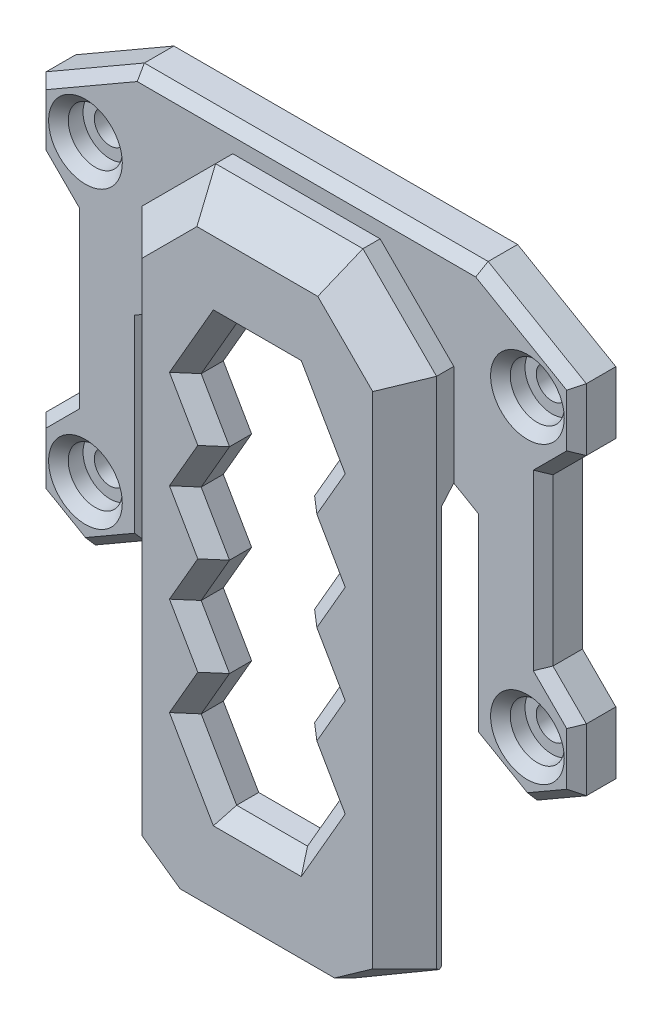
SolidWorks part; units mm, degrees
ref_plane "Front Plane" through (0, 0, 0) normal (0, 0, 1) x (1, 0, 0)
ref_plane "Top Plane" through (0, 0, 0) normal (0, 1, 0) x (1, 0, 0)
ref_plane "Right Plane" through (0, 0, 0) normal (1, 0, 0) x (0, 0, -1)
sketch "Sketch1" plane through (0, 0, 0) normal (0, 0, 1) x (1, 0, 0)
  line L0 (17.5, 0) -> (-17.5, 0)
  line L1 (-17.5, 0) -> (-27.5, -5.7735)
  line L2 (-27.5, -5.7735) -> (-27.5, -12.1132)
  line L3 (-27.5, -12.1132) -> (-24.1, -15.5132)
  line L4 (-24.1, -15.5132) -> (-24.1, -32.3735)
  line L5 (-24.1, -32.3735) -> (-27.5, -35.7735)
  line L6 (-27.5, -35.7735) -> (-27.5, -42.1132)
  line L7 (-27.5, -42.1132) -> (-22.5, -45)
  line L9 (-17.5, -42.1132) -> (-17.5, -20)
  line L10 (-4.5096, -12.5) -> (4.5096, -12.5)
  line L11 (0, -12.5) -> (0, 0) construction
  line L12 (-22.5, -45) -> (-17.5, -42.1132)
  line L13 (22.5, -45) -> (17.5, -42.1132)
  line L14 (17.5, -42.1132) -> (17.5, -20)
  line L15 (27.5, -42.1132) -> (22.5, -45)
  line L16 (27.5, -35.7735) -> (27.5, -42.1132)
  line L17 (24.1, -32.3735) -> (27.5, -35.7735)
  line L18 (24.1, -15.5132) -> (24.1, -32.3735)
  line L19 (27.5, -12.1132) -> (24.1, -15.5132)
  line L20 (27.5, -5.7735) -> (27.5, -12.1132)
  line L21 (17.5, 0) -> (27.5, -5.7735)
  line L22 (-17.5, -20) -> (-4.5096, -12.5)
  line L23 (4.5096, -12.5) -> (17.5, -20)
  circle A0 centre (-22.5, -8.9434) radius 1.6
  circle A1 centre (-22.5, -38.9434) radius 1.6
  circle A4 centre (22.5, -38.9434) radius 1.6
  circle A5 centre (22.5, -8.9434) radius 1.6
  point P18 (-27.5, -38.9434)
  point P35 (-27.5, -8.9434)
  dimension "D5" = 3.2
  dimension "D11" = 7.5
  dimension "D1" = 17.5
  dimension "D2" = 150
  dimension "D3" = 135
  dimension "D4" = 22.5
  dimension "D6" = 30
  dimension "D7" = 60
  dimension "D8" = 10
  dimension "D9" = 120
  dimension "D10" = 45
  dimension "D12" = 12.5
  dimension "D13" = 150
extrude "Boss-Extrude1" add sketch "Sketch1" along normal blind 4
sketch "Sketch2" plane through (0, 0, 4) normal (0, 0, 1) x (1, 0, 0)
  circle A0 centre (-22.5, -8.9434) radius 2.75
  circle A1 centre (22.5, -8.9434) radius 2.75
  circle A2 centre (22.5, -38.9434) radius 2.75
  circle A3 centre (-22.5, -38.9434) radius 2.75
  dimension "D1" = 5.5
extrude "Cut-Extrude1" cut sketch "Sketch2" against normal blind 2.5
chamfer "Chamfer1" distance 1 angle 45 21 edges at (-19.75, -38.9434, 4) (25.25, -38.9434, 4) (25.25, -8.9434, 4) (-19.75, -8.9434, 4) (-20, -43.5566, 4) (-25, -43.5566, 4) (20, -43.5566, 4) (25, -43.5566, 4) (27.5, -38.9434, 4) (-27.5, -38.9434, 4) (-25.8, -34.0735, 4) (25.8, -34.0735, 4) (24.1, -23.9434, 4) (25.8, -13.8132, 4) (-24.1, -23.9434, 4) (-25.8, -13.8132, 4) (27.5, -8.9434, 4) (22.5, -2.8868, 4) (-27.5, -8.9434, 4) (-22.5, -2.8868, 4) (0, 0, 4)
sketch "Sketch3" plane through (0, 0, 4) normal (0, 0, 1) x (1, 0, 0)
  line L1 (-7.5, -2.5) -> (7.5, -2.5)
  line L2 (-15, -10) -> (-15, -18.5566)
  line L4 (15, -10) -> (15, -18.5566)
  line L6 (-15, -10) -> (-7.5, -2.5)
  line L7 (7.5, -2.5) -> (15, -10)
  line L8 (4.5096, -12.5) -> (17.5, -20) construction
  line L9 (-17.5, -20) -> (-4.5096, -12.5) construction
  line L10 (-4.5096, -12.5) -> (4.5096, -12.5) construction
  line L11 (4.5096, -12.5) -> (15, -18.5566)
  line L12 (-15, -18.5566) -> (-4.5096, -12.5)
  line L13 (-4.5096, -12.5) -> (4.5096, -12.5)
  point P0 (-15, -2.5)
  point P3 (15, -2.5)
  dimension "D1" = 10
  dimension "D2" = 15
extrude "Boss-Extrude2" add sketch "Sketch3" along normal blind 5
chamfer "Chamfer2" distance 3.25 angle 45 5 edges at (15, -14.2783, 9) (-15, -14.2783, 9) (11.25, -6.25, 9) (0, -2.5, 9) (-11.25, -6.25, 9)
sketch "Sketch4" plane through (0, -12.5, 0) normal (0, -1, 0) x (1, 0, 0)
  line L0 (-11.75, 9) -> (-15, 5.75) construction
  line L1 (-11.75, 9) -> (-4.5096, 9) construction
  line L2 (-4.5096, 9) -> (4.5096, 9) construction
  line L3 (4.5096, 9) -> (11.75, 9) construction
  line L4 (15, 5.75) -> (11.75, 9) construction
  line L5 (-11.75, 9) -> (-15, 5.75)
  line L6 (-11.75, 9) -> (-4.5096, 9)
  line L7 (-4.5096, 9) -> (4.5096, 9)
  line L8 (4.5096, 9) -> (11.75, 9)
  line L9 (15, 5.75) -> (11.75, 9)
  line L10 (-15, 5.25) -> (15, 5.25)
  line L11 (15, 5.75) -> (15, 4) construction
  line L12 (-15, 5.75) -> (-15, 4) construction
  line L13 (15, 5.75) -> (15, 5.25)
  line L14 (-15, 5.75) -> (-15, 5.25)
  dimension "D1" = 0.5
extrude "Boss-Extrude3" add sketch "Sketch4" along normal blind 52.5
chamfer "Chamfer3" distance 2.75 angle 45 6 edges at (13.375, -65, 7.375) (0, -65, 5.25) (-13.375, -65, 7.375) (-9.7548, -15.5283, 5.25) (9.7548, -15.5283, 5.25) (0, -12.5, 5.25)
sketch "Sketch5" plane through (0, 0, 9) normal (0, 0, 1) x (1, 0, 0)
  line L0 (7.2169, -30) -> (3.6084, -23.75)
  line L1 (7.2169, -20) -> (3.6084, -13.75)
  line L2 (3.6084, -13.75) -> (-3.6084, -13.75)
  line L3 (-3.6084, -13.75) -> (-7.2169, -20)
  line L4 (-7.2169, -20) -> (-3.6084, -26.25)
  line L5 (-3.6084, -26.25) -> (3.6084, -26.25)
  line L6 (3.6084, -26.25) -> (7.2169, -20)
  line L7 (3.6084, -23.75) -> (-3.6084, -23.75)
  line L8 (-3.6084, -23.75) -> (-7.2169, -30)
  line L9 (-7.2169, -30) -> (-3.6084, -36.25)
  line L10 (-3.6084, -36.25) -> (3.6084, -36.25)
  line L11 (3.6084, -36.25) -> (7.2169, -30)
  line L12 (7.2169, -40) -> (3.6084, -33.75)
  line L13 (3.6084, -33.75) -> (-3.6084, -33.75)
  line L14 (-3.6084, -33.75) -> (-7.2169, -40)
  line L15 (-7.2169, -40) -> (-3.6084, -46.25)
  line L16 (-3.6084, -46.25) -> (3.6084, -46.25)
  line L17 (3.6084, -46.25) -> (7.2169, -40)
  line L18 (7.2169, -50) -> (3.6084, -43.75)
  line L19 (3.6084, -43.75) -> (-3.6084, -43.75)
  line L20 (-3.6084, -43.75) -> (-7.2169, -50)
  line L21 (-7.2169, -50) -> (-3.6084, -56.25)
  line L22 (-3.6084, -56.25) -> (3.6084, -56.25)
  line L23 (3.6084, -56.25) -> (7.2169, -50)
  line L24 (7.2169, -20) -> (7.2169, -30) construction
  circle A0 centre (0, -20) radius 6.25 construction
  circle A1 centre (0, -30) radius 6.25 construction
  circle A2 centre (0, -40) radius 6.25 construction
  circle A3 centre (0, -50) radius 6.25 construction
  dimension "D1" = 12.5
  dimension "D2" = 20
  dimension "D4" = 10
  dimension "D3" = 4
extrude "Cut-Extrude3" cut sketch "Sketch5" against normal blind 50 contours L22 L23 L18 L17 L16 L15 L20 L21 | L19 L20 L15 L16 L17 L18 | L13 L14 L9 L10 L11 L12 | L14 L13 L12 L11 L0 L6 L5 L4 L8 L9 | L7 L8 L4 L5 L6 L0 | L8 L7 L0 L6 L1 L2 L3 L4 | L16 L17 L12 L13 L14 L15 region at (0, -30, 9) region at (0, -25, 9) region at (0, -19.1406, 9) region at (0, -35, 9) region at (0, -50.8594, 9) region at (0, -45, 9)
chamfer "Chamfer4" distance 1.5 angle 45 18 edges at (5.7735, -47.5, 9) (5.7735, -42.5, 9) (5.7735, -37.5, 9) (5.7735, -32.5, 9) (5.7735, -27.5, 9) (5.7735, -22.5, 9) (5.4127, -16.875, 9) (0, -13.75, 9) (-5.4127, -16.875, 9) (-5.7735, -22.5, 9) (-5.7735, -27.5, 9) (-5.7735, -32.5, 9) (-5.7735, -37.5, 9) (-5.7735, -42.5, 9) (-5.7735, -47.5, 9) (-5.4127, -53.125, 9) (0, -56.25, 9) (5.4127, -53.125, 9)
sketch "Sketch6" plane through (0, 0, 5.25) normal (0, 0, -1) x (-1, 0, 0)
  line L1 (-15, -62.25) -> (15, -62.25)
  line L2 (-15, -62.25) -> (-15, -56.25)
  line L3 (-15, -56.25) -> (15, -56.25)
  line L4 (15, -62.25) -> (15, -56.25)
  line L5 (3.6084, -56.25) -> (-3.6084, -56.25) construction
  line L6 (15, -62.25) -> (15, -21.7321) construction
  line L7 (-15, -62.25) -> (15, -62.25) construction
extrude "Boss-Extrude4" add sketch "Sketch6" along normal blind 2
chamfer "Chamfer5" distance 2 angle 45 4 edges at (0, -56.25, 3.25) (-15, -59.25, 3.25) (0, -62.25, 3.25) (15, -59.25, 3.25)
